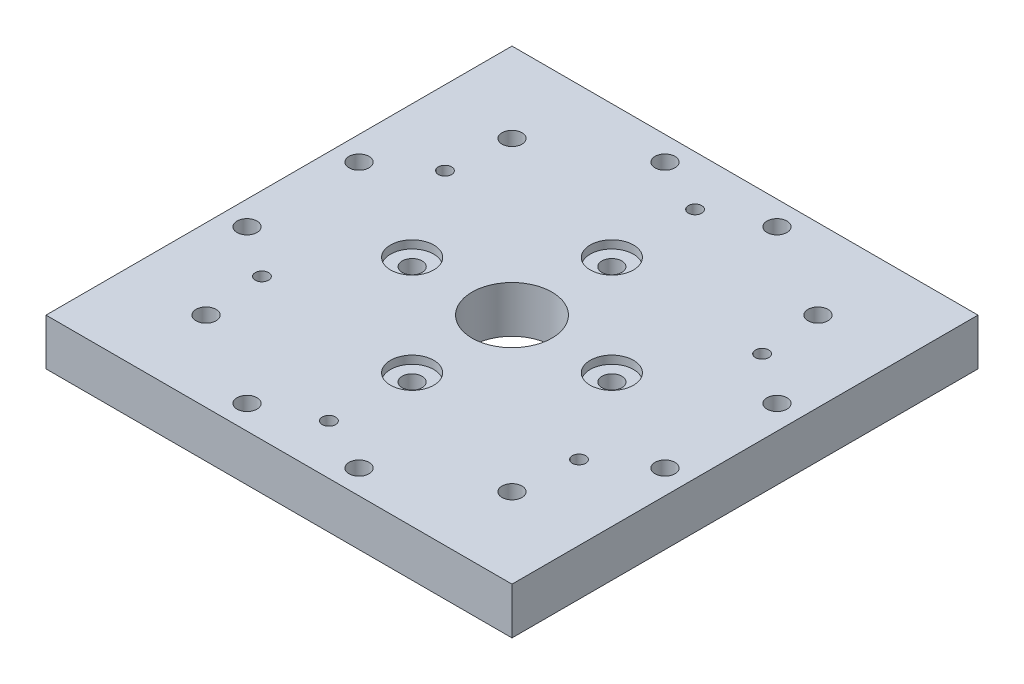
SolidWorks part; units mm, degrees
ref_plane "Front Plane" through (0, 0, 0) normal (0, 0, 1) x (1, 0, 0)
ref_plane "Top Plane" through (0, 0, 0) normal (0, 1, 0) x (1, 0, 0)
ref_plane "Right Plane" through (0, 0, 0) normal (1, 0, 0) x (0, 0, -1)
sketch "Sketch1" plane through (0, 0, 0) normal (0, 1, 0) x (1, 0, 0)
  line L0 (-49.4318, 0) -> (0, 0) construction
  line L1 (0, 0) -> (-47.2333, -12.6561) construction
  line L2 (-35, 35) -> (35, 35)
  line L3 (-35, 35) -> (-35, -35)
  line L4 (35, 35) -> (35, -35)
  line L5 (-35, -35) -> (35, -35)
  circle A0 centre (0, 0) radius 35 construction
  circle A1 centre (0, 0) radius 27.5 construction
  circle A2 centre (0, 0) radius 6
  circle A3 centre (0, 0) radius 15 construction
  circle A4 centre (0, 15) radius 1.5
  circle A5 centre (15, 0) radius 1.5
  circle A6 centre (0, -15) radius 1.5
  circle A7 centre (-15, 0) radius 1.5
  circle A11 centre (0, 0) radius 32.5 construction
  circle A12 centre (-31.3926, -8.4116) radius 1.5
  circle A13 centre (-31.3926, 8.4116) radius 1.5
  circle A14 centre (-22.981, 22.981) radius 1.5
  circle A15 centre (-8.4116, 31.3926) radius 1.5
  circle A16 centre (8.4116, 31.3926) radius 1.5
  circle A17 centre (22.981, 22.981) radius 1.5
  circle A18 centre (31.3926, 8.4116) radius 1.5
  circle A19 centre (31.3926, -8.4116) radius 1.5
  circle A20 centre (22.981, -22.981) radius 1.5
  circle A21 centre (8.4116, -31.3926) radius 1.5
  circle A22 centre (-8.4116, -31.3926) radius 1.5
  circle A23 centre (-22.981, -22.981) radius 1.5
  circle A24 centre (0, 27.5) radius 1
  circle A25 centre (23.8157, 13.75) radius 1
  circle A26 centre (23.8157, -13.75) radius 1
  circle A27 centre (0, -27.5) radius 1
  circle A28 centre (-23.8157, -13.75) radius 1
  circle A29 centre (-23.8157, 13.75) radius 1
  point P17 (0, 0)
  point P44 (0, 0)
  point P57 (0, 0)
  dimension "D1" = 70
  dimension "D2" = 55
  dimension "D3" = 12
  dimension "D4" = 3
  dimension "D6" = 30
  dimension "D7" = 65
  dimension "D9" = 3
  dimension "D11" = 2
  dimension "D8" = 15
  dimension "D5" = 4
  dimension "D10" = 12
  dimension "D12" = 6
extrude "Boss-Extrude1" add sketch "Sketch1" along normal blind 7
sketch "Sketch2" plane through (0, 7, 0) normal (0, 1, 0) x (1, 0, 0)
  circle A0 centre (0, 0) radius 15 construction
  circle A1 centre (0, 15) radius 3.25
  circle A2 centre (15, 0) radius 3.25
  circle A3 centre (0, -15) radius 3.25
  circle A4 centre (-15, 0) radius 3.25
  point P15 (0, 0)
  dimension "D1" = 6.5
  dimension "D2" = 4
extrude "Cut-Extrude1" cut sketch "Sketch2" against normal blind 1.2
